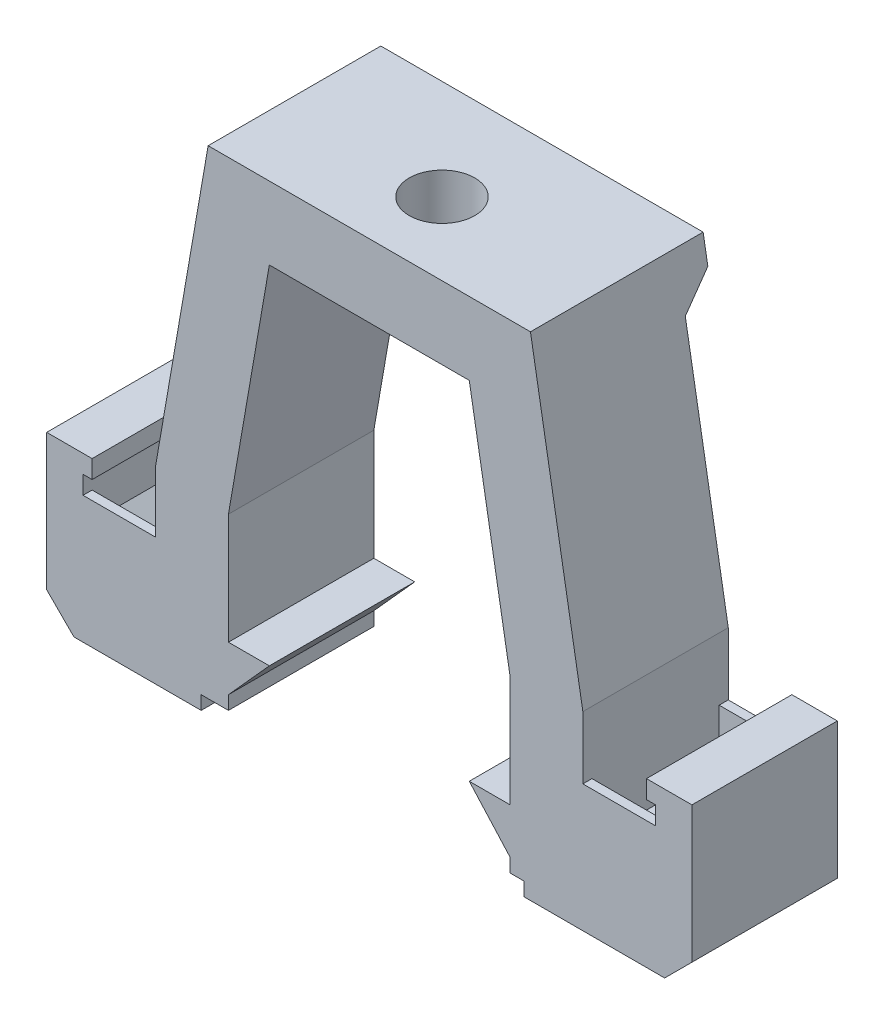
SolidWorks part; units mm, degrees
ref_plane "Front Plane" through (0, 0, 0) normal (0, 0, 1) x (1, 0, 0)
ref_plane "Top Plane" through (0, 0, 0) normal (0, 1, 0) x (1, 0, 0)
ref_plane "Right Plane" through (0, 0, 0) normal (1, 0, 0) x (0, 0, -1)
sketch "Sketch1" plane through (0, 0, 0) normal (0, 0, 1) x (1, 0, 0)
  line L0 (8.8672, 0) -> (-8.8672, 0)
  line L1 (-8.8672, 0) -> (-11.75, -16.6564)
  line L2 (-11.75, -16.6564) -> (-11.75, -27.1)
  line L3 (-11.75, -27.1) -> (-9.25, -27.1)
  line L4 (-7.75, -26.35) -> (-7.75, -25.6)
  line L5 (-7.75, -25.6) -> (-5.5, -23.1)
  line L6 (-5.5, -23.1) -> (-7.75, -23.1)
  line L7 (-7.75, -23.1) -> (-7.75, -17)
  line L8 (-7.75, -17) -> (-5.5, -4)
  line L9 (-5.5, -4) -> (5.5, -4)
  line L10 (0, 0) -> (0, -7.0392) construction
  line L11 (7.75, -17) -> (5.5, -4)
  line L12 (7.75, -23.1) -> (7.75, -17)
  line L13 (5.5, -23.1) -> (7.75, -23.1)
  line L14 (7.75, -25.6) -> (5.5, -23.1)
  line L15 (7.75, -26.35) -> (7.75, -25.6)
  line L16 (11.75, -27.1) -> (8.5, -27.1)
  line L17 (11.75, -16.6564) -> (11.75, -27.1)
  line L18 (8.8672, 0) -> (11.75, -16.6564)
  line L19 (-7.75, -26.35) -> (-9.25, -26.35)
  line L20 (-9.25, -26.35) -> (-9.25, -27.1)
  line L21 (7.75, -26.35) -> (8.5, -26.35)
  line L22 (8.5, -26.35) -> (8.5, -27.1)
  dimension "D1" = 19.1
  dimension "D5" = 4
  dimension "D2" = 2.5
  dimension "D3" = 2.25
  dimension "D4" = 4
  dimension "D8" = 1.5
  dimension "D6" = 11
  dimension "D7" = 13
  dimension "D9" = 15.5
  dimension "D10" = 0.75
  dimension "D11" = 1.5
extrude "Boss-Extrude1" add sketch "Sketch1" along normal blind 8
sketch "Sketch2" plane through (0, 0, 0) normal (0, 1, 0) x (1, 0, 0)
  line L0 (0, 0) -> (0, -8) construction
  line L1 (8.8672, 0) -> (-8.8672, 0) construction
  line L2 (8.8672, -8) -> (-8.8672, -8) construction
  line L7 (0, -6.4749) -> (0, -1.5251) construction
  line L8 (2.4749, -4) -> (-2.4749, -4) construction
  circle A0 centre (0, -4) radius 1.8
  point P1 (0, -4)
  point P8 (0, -4)
  dimension "D1" = 3.6
extrude "Cut-Extrude1" cut sketch "Sketch2" against normal through all
sketch "Sketch7" plane through (0, 0, 0) normal (0, 0, -1) x (-1, 0, 0)
  line L0 (-11.75, -27.1) -> (-16.25, -27.1)
  line L1 (-17.75, -25.6) -> (-17.75, -18.1)
  line L2 (-17.75, -18.1) -> (-15.25, -18.1)
  line L3 (-15.75, -19.1) -> (-15.75, -21.6)
  line L4 (-14.25, -23.1) -> (-11.75, -23.1)
  line L5 (-11.75, -23.1) -> (-11.75, -27.1)
  line L6 (0, 0) -> (0, -10.2096) construction
  line L14 (-15.25, -18.1) -> (-15.25, -19.1)
  line L15 (-15.25, -19.1) -> (-15.75, -19.1)
  line L25 (-15.75, -21.6) -> (-14.25, -23.1)
  line L26 (-16.25, -27.1) -> (-17.75, -25.6)
  line L27 (-11.75, -27.1) -> (-11.75, -16.6564) construction
  line L28 (16.25, -27.1) -> (17.75, -25.6)
  line L29 (15.75, -21.6) -> (14.25, -23.1)
  line L30 (15.25, -19.1) -> (15.75, -19.1)
  line L31 (15.25, -18.1) -> (15.25, -19.1)
  line L32 (11.75, -23.1) -> (11.75, -27.1)
  line L33 (14.25, -23.1) -> (11.75, -23.1)
  line L34 (15.75, -19.1) -> (15.75, -21.6)
  line L35 (17.75, -18.1) -> (15.25, -18.1)
  line L36 (17.75, -25.6) -> (17.75, -18.1)
  line L37 (11.75, -27.1) -> (16.25, -27.1)
  point P1 (-17.75, -27.1)
  point P6 (-15.75, -23.1)
  point P10 (15.75, -23.1)
  point P11 (17.75, -27.1)
  point P26 (-15.25, -18.6)
  dimension "D1" = 4
  dimension "D2" = 2
  dimension "D3" = 1
  dimension "D6" = 0.5
  dimension "D7" = 4
  dimension "D8" = 5
extrude "Boss-Extrude4" add sketch "Sketch7" against normal up to surface (8 mm away) up to face at (-0.0682, -19.6688, 8)
sketch "Sketch8" plane through (0, 0, 0) normal (0, 0, -1) x (-1, 0, 0)
  line L0 (-11.75, -23.1) -> (-11.75, -16.6564) construction
  line L1 (-11.75, -23.1) -> (-14.25, -23.1) construction
  line L2 (-14.25, -23.1) -> (-15.75, -21.6) construction
  line L3 (-15.75, -21.6) -> (-15.75, -19.1) construction
  line L4 (-11.75, -23.1) -> (-11.75, -20.1)
  line L5 (-11.75, -23.1) -> (-14.25, -23.1)
  line L6 (-14.25, -23.1) -> (-15.75, -21.6)
  line L7 (-15.75, -21.6) -> (-15.75, -20.1)
  line L8 (-15.75, -20.1) -> (-11.75, -20.1)
  line L9 (0, 0) -> (0, -7.2694) construction
  line L10 (15.75, -20.1) -> (11.75, -20.1)
  line L11 (15.75, -21.6) -> (15.75, -20.1)
  line L12 (14.25, -23.1) -> (15.75, -21.6)
  line L13 (11.75, -23.1) -> (14.25, -23.1)
  line L14 (11.75, -23.1) -> (11.75, -20.1)
  dimension "D1" = 3
extrude "Boss-Extrude5" add sketch "Sketch8" against normal blind 0.5
extrude "Boss-Extrude6" add sketch "Sketch8<2>" along normal blind 0.5 from surface starting at face at (-0.0395, -20.2188, 8)
sketch "Sketch8<2>" plane through (0, 0, 0) normal (0, 0, -1) x (-1, 0, 0) same geometry as "Sketch8"
sketch "Sketch3" [suppressed] plane through (0, 0, 8) normal (0, 0, 1) x (1, 0, 0)
  line L0 (-14.75, -20.6) -> (-23.75, -20.6)
  line L1 (-23.75, -20.6) -> (-23.75, -23.6)
  line L2 (-23.75, -23.6) -> (-14.75, -23.6)
  line L3 (-14.75, -23.6) -> (-11.75, -26.6)
  line L4 (-11.75, -16.6564) -> (-11.75, -21.6) construction
  line L5 (-11.75, -26.6) -> (-11.75, -17.6)
  line L6 (-11.75, -17.6) -> (-14.75, -20.6)
  line L7 (0, 0) -> (0, -11.0245) construction
  line L8 (11.75, -17.6) -> (14.75, -20.6)
  line L9 (11.75, -26.6) -> (11.75, -17.6)
  line L10 (14.75, -23.6) -> (11.75, -26.6)
  line L11 (23.75, -23.6) -> (14.75, -23.6)
  line L12 (23.75, -20.6) -> (23.75, -23.6)
  line L13 (14.75, -20.6) -> (23.75, -20.6)
  dimension "D1" = 45
  dimension "D2" = 12
  dimension "D3" = 3
  dimension "D4" = 2
  dimension "D5" = 3
extrude "Boss-Extrude2" [suppressed] add sketch "Sketch3" against normal up to surface (8 mm away)
chamfer "Chamfer1" [suppressed] distance 2 angle 45
chamfer "Chamfer2" [suppressed] distance 0.5 angle 45
sketch "Sketch5" plane through (0, 0, 0) normal (0, 0, -1) x (-1, 0, 0)
  line L1 (-8.8672, 0) -> (8.8672, 0) construction
  line L2 (8.8672, 0) -> (-8.8672, 0)
  line L3 (-8.8672, 0) -> (-9.1268, -1.5)
  line L4 (-11.75, -16.6564) -> (-8.8672, 0) construction
  line L5 (-9.1268, -1.5) -> (9.1268, -1.5)
  line L7 (9.1268, -1.5) -> (8.8672, 0)
  line L9 (8.8672, 0) -> (11.75, -16.6564) construction
  dimension "D1" = 1.5
extrude "Boss-Extrude3" add sketch "Sketch5" along normal blind 1.5
chamfer "Chamfer3" distance 1.5 angle 45 1 edges at (0, -1.5, 0)
